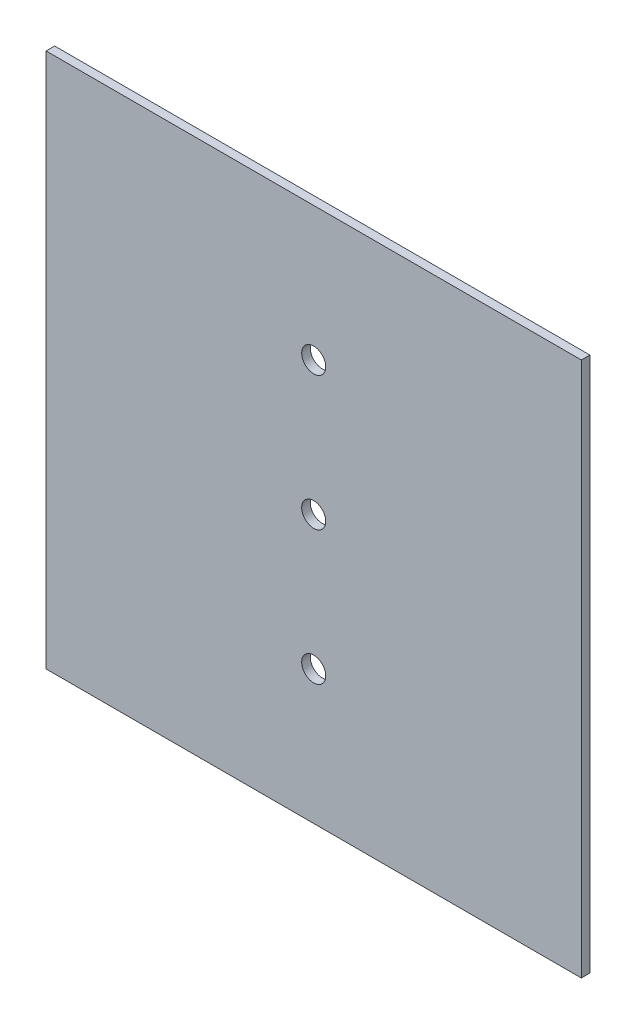
SolidWorks part; units mm, degrees
material "Copper"
ref_plane "Front Plane" through (0, 0, 0) normal (0, 0, 1) x (1, 0, 0)
ref_plane "Top Plane" through (0, 0, 0) normal (0, 1, 0) x (1, 0, 0)
ref_plane "Right Plane" through (0, 0, 0) normal (1, 0, 0) x (0, 0, -1)
sketch "Sketch1" plane through (0, 0, 0) normal (0, 0, 1) x (1, 0, 0)
  line L1 (-50, -50) -> (50, -50)
  line L2 (-50, -50) -> (-50, 50)
  line L3 (-50, 50) -> (50, 50)
  line L4 (50, -50) -> (50, 50)
  line L5 (-50, -50) -> (50, 50) construction
  line L6 (-50, 50) -> (50, -50) construction
  dimension "D1" = 100
extrude "Boss-Extrude1" add sketch "Sketch1" along normal blind 1.6
sketch "Sketch2" [suppressed] plane through (0, 0, 1.6) normal (0, 0, 1) x (1, 0, 0)
  circle A0 centre (0, 0) radius 50
  line M2 (50, -50) -> (50, 50)
  line M3 (50, 50) -> (-50, 50)
  line M4 (-50, 50) -> (-50, -50)
  line M5 (-50, -50) -> (50, -50)
  dimension "D1" = 100
extrude "Cut-Extrude1" [suppressed] cut sketch "Sketch2" against normal blind 1.6 contours A0 M3 M4 | A0 M4 M5 | A0 M5 M2 | A0 M2 M3
sketch "Sketch3" plane through (0, 0, 0) normal (0, 0, -1) x (-1, 0, 0)
  circle A3 centre (0, 0) radius 2.2479
  circle A4 centre (0, -25) radius 2.2479 construction
  circle A5 centre (0, -25) radius 2.2479
  circle A6 centre (0, 25) radius 2.2479 construction
  circle A7 centre (0, 25) radius 2.2479
  point P1 (0, 0)
  dimension "D1" = 4.4958
extrude "Cut-Extrude2" cut sketch "Sketch3" against normal up to surface (1.6 mm away) up to face at (0, 0, 1.6)
